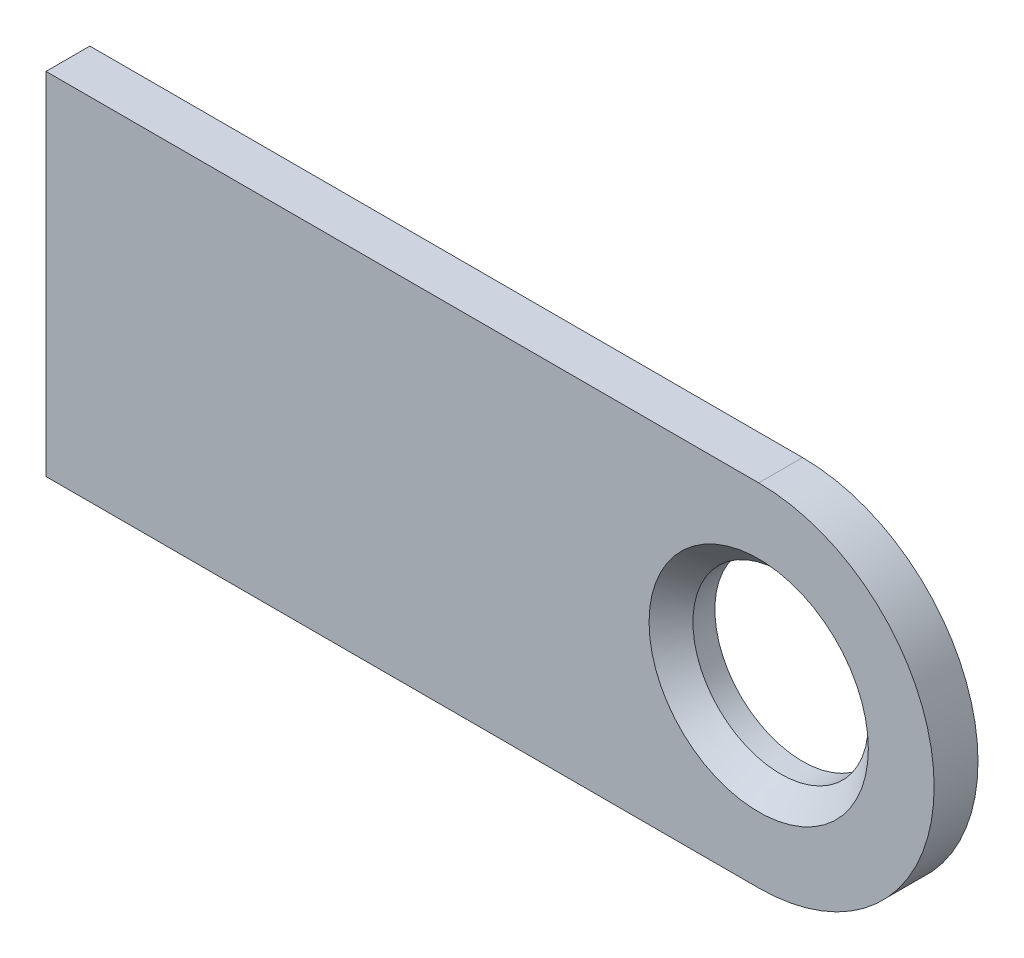
SolidWorks part; units mm, degrees
material "AISI 1020"
ref_plane "Спереди" through (0, 0, 0) normal (0, 0, 1) x (1, 0, 0)
ref_plane "Сверху" through (0, 0, 0) normal (0, 1, 0) x (1, 0, 0)
ref_plane "Справа" through (0, 0, 0) normal (1, 0, 0) x (0, 0, -1)
sketch "Эскиз1" plane through (0, 0, 0) normal (0, 0, 1) x (1, 0, 0)
  line L0 (0, 16) -> (-65, 16)
  line L1 (-65, 16) -> (-65, -16)
  line L2 (-65, -16) -> (0, -16)
  circle A0 centre (0, 0) radius 8 construction
  circle A1 centre (0, 0) radius 8
  arc A2 (0, -16) -> (0, 16) centre (0, 0) ccw
  arc A3 (-15.6213, 3.4604) -> (9.4853, -12.8852) centre (0, 0) ccw construction
  dimension "D1" = 65
base flange "Базовая кромка1" sketch "Эскиз1" thickness 4 reverse thickness direction yes parameters "D1"=0.74
chamfer "Фаска1" distance 2 angle 45 1 edges at (8, 0, 4)
sketch "Сгиб-Линии1" [suppressed] plane through (0, 0, 0) normal (0, 1, 0) x (1, 0, 0)
sketch "Граничная рамка1" [suppressed] plane through (0, 0, 0) normal (0, 1, 0) x (1, 0, 0)
sheet metal parameters "Листовой металл3" thickness 4 parameters "D1"=0.74
flat pattern "Развертка3" [suppressed]
sketch "Сгиб-Линии2" plane through (0, 0, 0) normal (0, 1, 0) x (1, 0, 0)
sketch3d "Граничная рамка2" [suppressed]
  line L0 (65, 16, 0) -> (-16, 16, 0) construction
  line L1 (65, -16, 0) -> (-16, -16, 0) construction
  line L2 (65, 16, 0) -> (65, -16, 0) construction
  line L3 (-16, 16, 0) -> (-16, -16, 0) construction
